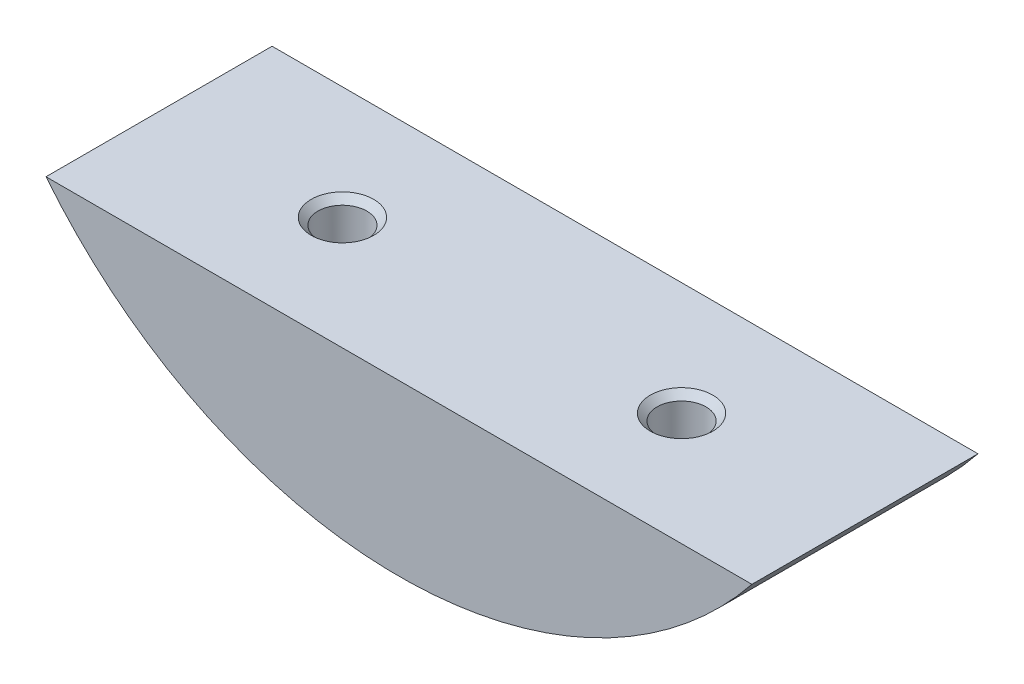
SolidWorks part; units mm, degrees
material "ABS"
ref_plane "Front Plane" through (0, 0, 0) normal (0, 0, 1) x (1, 0, 0)
ref_plane "Top Plane" through (0, 0, 0) normal (0, 1, 0) x (1, 0, 0)
ref_plane "Right Plane" through (0, 0, 0) normal (1, 0, 0) x (0, 0, -1)
sketch "Sketch1" plane through (0, 0, 0) normal (0, 0, 1) x (1, 0, 0)
  line L0 (0, 0) -> (79.3115, 0)
  arc A0 (0, 0) -> (79.3115, 0) centre (39.6557, 31.75) ccw
  dimension "D1" = 50.8
  dimension "D2" = 31.75
extrude "Boss-Extrude1" add sketch "Sketch1" along normal blind 25.4
sketch "Sketch2" plane through (0, 0, 0) normal (0, 1, 0) x (1, 0, 0)
  line L0 (0, -12.7) -> (20.6057, -12.7) construction
  line L1 (0, -25.4) -> (0, 0) construction
  line L2 (20.6057, -12.7) -> (58.7057, -12.7) construction
  line L3 (58.7057, -12.7) -> (79.3115, -12.7) construction
  line L4 (79.3115, -25.4) -> (79.3115, 0) construction
  circle A0 centre (20.6057, -12.7) radius 2
  circle A1 centre (58.7057, -12.7) radius 2
  dimension "D2" = 4
  dimension "D1" = 38.1
extrude "Cut-Extrude1" cut sketch "Sketch2" against normal through all both and the other way through all
sketch "Sketch3" plane through (0, 0, 0) normal (0, 1, 0) x (1, 0, 0)
  circle A0 centre (20.6057, -12.7) radius 2.75
  circle A1 centre (58.7057, -12.7) radius 2.75
  dimension "D1" = 5.5
extrude "Cut-Extrude2" cut sketch "Sketch3" against normal through all
chamfer "Chamfer1" distance 0.762 angle 45 2 edges at (20.6057, 0, 15.45) (58.7057, 0, 15.45)
